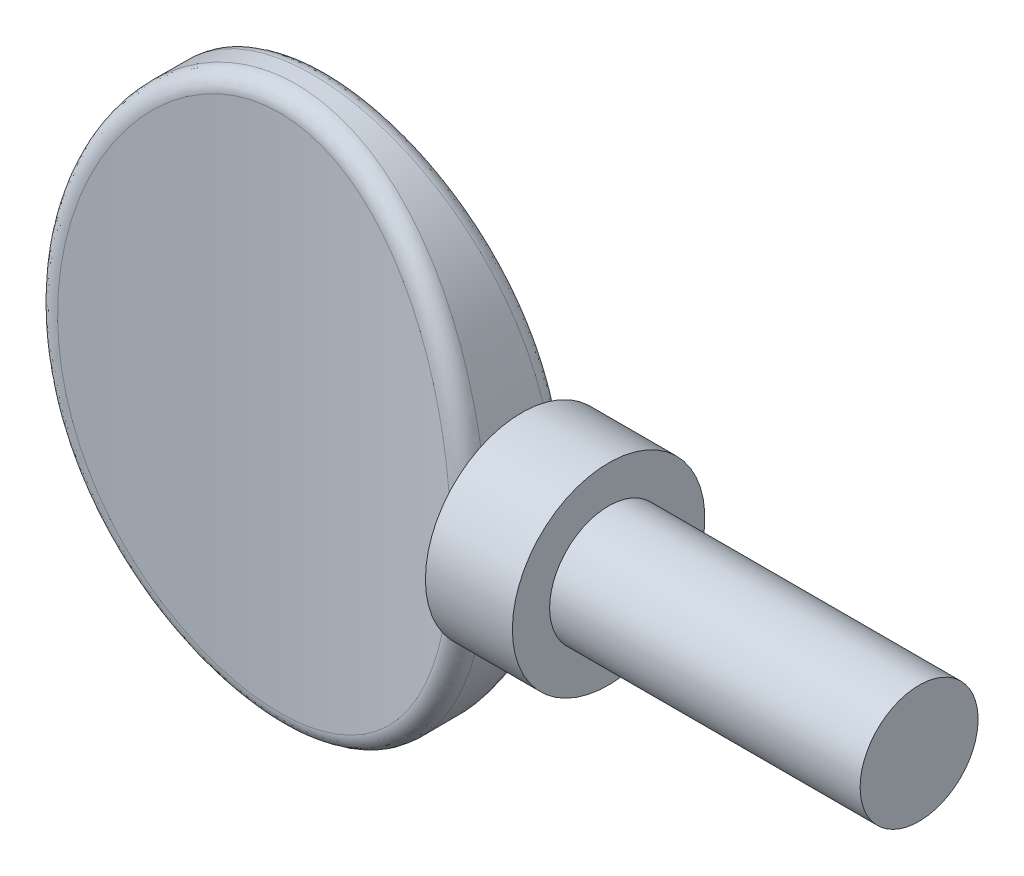
SolidWorks part; units mm, degrees
ref_plane "Front" through (0, 0, 0) normal (0, 0, 1) x (1, 0, 0)
ref_plane "Top" through (0, 0, 0) normal (0, 1, 0) x (1, 0, 0)
ref_plane "Right" through (0, 0, 0) normal (1, 0, 0) x (0, 0, -1)
ref_axis "Axis1" through (-50, 0, 0) along (1, 0, 0)
sketch "Sketch1" plane through (0, 0, 0) normal (0, 0, 1) x (1, 0, 0)
  line L0 (0, 0) -> (25.146, 0) construction
  line L1 (12.446, -3.937) -> (12.446, 3.937)
  ellipse E0 centre (0, 0) end of major axis (0, 11.303) minor radius 8.89
  dimension "D2" = 3.556
extrude "Extrude1" add sketch "Sketch1" along normal mid plane 4.572
sketch "Sketch2" plane through (0, 0, 0) normal (0, 1, 0) x (1, 0, 0)
  line L0 (8.89, 2.286) -> (-8.89, 2.286) construction
  line L1 (0, 0) -> (0, 1.1721) construction
  line L2 (-1.7991, 0) -> (2.0444, 0) construction
  line L3 (-8.89, -2.286) -> (8.89, -2.286) construction
  line L6 (-8.89, 2.286) -> (-8.89, -2.286)
  line L7 (8.89, 2.286) -> (8.89, -2.286)
  arc A0 (-8.89, 2.286) -> (8.89, 2.286) centre (0, 32.766) ccw
  arc A1 (-8.89, -2.286) -> (8.89, -2.286) centre (0, -32.766) cw
extrude "Cut-Extrude1" cut sketch "Sketch2" against normal through all and the other way through all flip side to cut
fillet "Fillet3" radius 0.6773 2 edges at (-8.875, -0.6558, 2.2816) (-1.5369, -11.1328, -1.0532)
sketch "Sketch3" plane through (0, 0, 0) normal (0, 1, 0) x (1, 0, 0)
  line L0 (12.446, 3.937) -> (12.446, 2.413)
  line L1 (0, 0) -> (21.0288, 0) construction
  line L2 (0, 0) -> (25.146, 0) construction
  line L3 (12.446, 2.413) -> (12.446, 0) construction
  line L4 (12.446, 2.413) -> (25.146, 2.413)
  line L5 (25.146, 2.413) -> (25.146, 0)
  line L6 (12.446, 3.937) -> (8.89, 3.937)
  line L7 (7.2364, 1.8517) -> (7.2364, 0)
  line L8 (8.89, 0) -> (8.89, 3.937) construction
  line L9 (7.2364, 0) -> (25.146, 0)
  arc A0 (8.89, 3.937) -> (7.2364, 1.8517) centre (6.7483, 3.937) cw
  arc A3 (-8.89, 2.286) -> (8.89, 2.286) centre (0, 32.766) ccw construction
  dimension "D1" = 7.874
revolve "Revolve1" add sketch "Sketch3" angle 360 about L0
cosmetic thread "Cosmetic Thread1" [suppressed]
sketch "Sketch4" plane through (0, 0, 0) normal (0, 0, 1) x (1, 0, 0)
  line L0 (0, 0) -> (27.7993, 0) construction
  line L1 (24.7823, 2.413) -> (25.146, 1.7831)
  line L2 (25.146, 1.7831) -> (25.5097, 2.413)
  line L3 (25.5097, 2.413) -> (25.5097, 3.1404)
  line L4 (25.5097, 3.1404) -> (24.7823, 3.1404)
  line L5 (24.7823, 3.1404) -> (24.7823, 2.413)
  dimension "D1" = 3.5662
  dimension "D2" = 4.826
revolve "Cut-Revolve10" [suppressed] cut sketch "Sketch4" angle 360 about L0
pattern_linear "LPattern10" [suppressed] count 12 along (-1, 0, 0) of bodies 109
equation "\"D2@Sketch1\" = \"B@Sketch1\" / 6"
equation "\"D1@Sketch3\" = \"E@Sketch1\""
equation "\"D1@Fillet3\" = \"C1@Sketch2\" / 3"
equation "\"D1@Sketch4\" = \"D2@Cosmetic Thread1\""
equation "\"D2@Sketch4\" = \"DIA@Sketch3\""
equation "\"D1@LPattern10\" = \"L@Sketch1\" / \"P@LPattern10\" "
